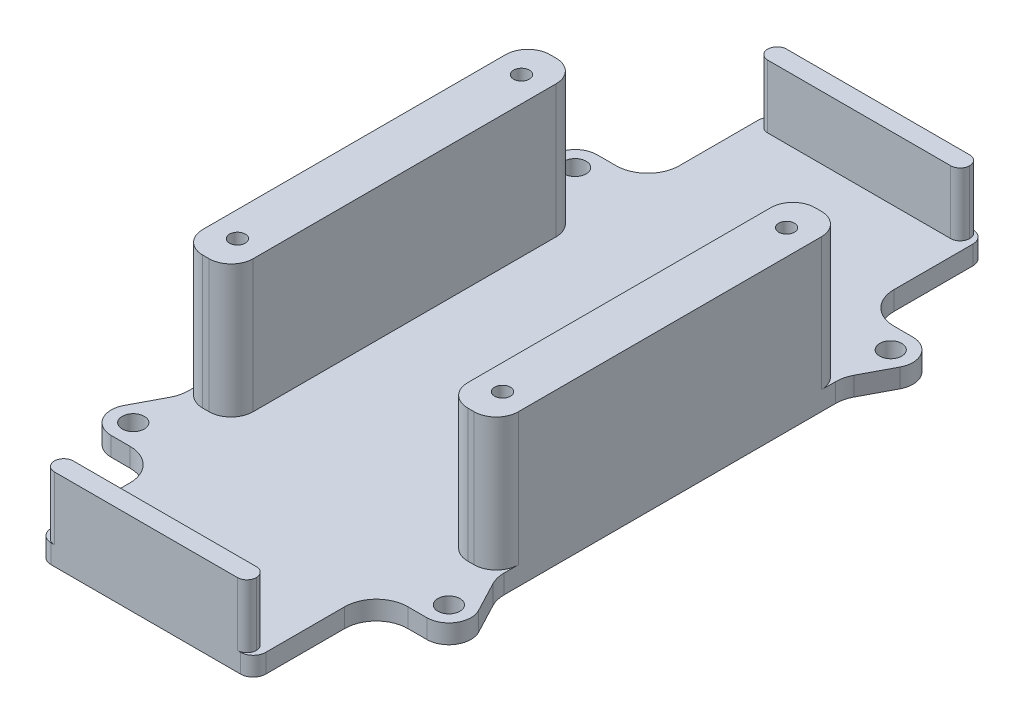
SolidWorks part; units mm, degrees
ref_plane "Спереди" through (0, 0, 0) normal (0, 0, 1) x (1, 0, 0)
ref_plane "Сверху" through (0, 0, 0) normal (0, 1, 0) x (1, 0, 0)
ref_plane "Справа" through (0, 0, 0) normal (1, 0, 0) x (0, 0, -1)
sketch "Эскиз1" plane through (0, 0, 0) normal (0, 1, 0) x (1, 0, 0)
  line L0 (0, 58) -> (0, -58) construction
  line L1 (-17, 58) -> (17, 58)
  line L2 (-25, 27.5) -> (-25, -27.5)
  line L3 (-17, -58) -> (17, -58)
  line L4 (25, 27.5) -> (25, -27.5)
  line L5 (-25, 27.5) -> (-17, 27.5)
  line L6 (-25, 0) -> (25, 0) construction
  line L7 (-17, 27.5) -> (-17, 58)
  line L8 (25, 27.5) -> (17, 27.5)
  line L9 (17, 27.5) -> (17, 58)
  line L10 (17, -27.5) -> (17, -58)
  line L11 (25, -27.5) -> (17, -27.5)
  line L12 (-17, -27.5) -> (-17, -58)
  line L13 (-25, -27.5) -> (-17, -27.5)
  point P8 (0, 0)
  dimension "D1" = 50
  dimension "D2" = 116
  dimension "D3" = 8
  dimension "D4" = 55
extrude "тело" add sketch "Эскиз1" along normal blind 3
sketch "Эскиз2" plane through (0, 3, 0) normal (0, 1, 0) x (1, 0, 0)
  line L0 (0, 58) -> (0, -58) construction
  line L3 (17, 58) -> (-17, 58) construction
  line L5 (-17, -58) -> (17, -58) construction
  line L7 (-25, 0) -> (25, 0) construction
  line L8 (-25, 27.5) -> (-25, -27.5) construction
  line L9 (25, -27.5) -> (25, 27.5) construction
  line L11 (-16, 58) -> (16, 58)
  line L12 (-16, 58) -> (-16, 55)
  line L13 (-16, 55) -> (16, 55)
  line L14 (16, 58) -> (16, 55)
  line L15 (-16, -58) -> (16, -58)
  line L16 (-16, -58) -> (-16, -55)
  line L17 (-16, -55) -> (16, -55)
  line L18 (16, -58) -> (16, -55)
  point P22 (0, 58)
  point P23 (0, -58)
  dimension "D1" = 110
  dimension "D2" = 32
extrude "выступы фиксации аккума" add sketch "Эскиз2" along normal blind 10
sketch "Эскиз9" plane through (0, 3, 0) normal (0, 1, 0) x (1, 0, 0)
  line L0 (0, 58) -> (0, -58) construction
  line L3 (-25, 0) -> (25, 0) construction
  line L5 (-25, 27.5) -> (-25, -27.5) construction
  line L6 (25, -27.5) -> (25, 27.5) construction
  line L7 (16, 58) -> (-16, 58) construction
  line L8 (-25, 27.5) -> (-17, 27.5)
  line L9 (-25, 27.5) -> (-25, -27.5)
  line L10 (-25, -27.5) -> (-17, -27.5)
  line L11 (-17, 27.5) -> (-17, -27.5)
  line L12 (25, 27.5) -> (17, 27.5)
  line L13 (25, 27.5) -> (25, -27.5)
  line L14 (25, -27.5) -> (17, -27.5)
  line L15 (17, 27.5) -> (17, -27.5)
  line L16 (-16, -58) -> (16, -58) construction
  point P20 (17, 0)
  point P21 (-17, 0)
  point P28 (0, 58)
  dimension "D1" = 34
  dimension "D2" = 55
  dimension "D3" = 8
extrude "выступы для крышки" add sketch "Эскиз9" along normal blind 21
sketch "Эскиз11" plane through (0, 24, 0) normal (0, 1, 0) x (1, 0, 0)
  line L0 (-21, 27.5) -> (-21, -27.5) construction
  line L1 (-17, 27.5) -> (-25, 27.5) construction
  line L2 (-25, -27.5) -> (-17, -27.5) construction
  line L4 (25, 27.5) -> (17, 27.5) construction
  line L5 (21, 27.5) -> (21, -27.5) construction
  line L6 (17, -27.5) -> (25, -27.5) construction
  line L8 (25, -27.5) -> (25, 27.5) construction
  line L9 (25, 0) -> (-25, 0) construction
  line L10 (-25, 27.5) -> (-25, -27.5) construction
  circle A0 centre (-21, 22.5) radius 1.25
  circle A1 centre (-21, -22.5) radius 1.25
  circle A2 centre (21, 22.5) radius 1.25
  circle A3 centre (21, -22.5) radius 1.25
  dimension "D2" = 2.5
  dimension "D1" = 45
extrude "отверстия под шурупы" cut sketch "Эскиз11" against normal blind 15
sketch "Эскиз12" plane through (0, 3, 0) normal (0, 1, 0) x (1, 0, 0)
  line L0 (0, 0) -> (0, 58) construction
  line L1 (16, 58) -> (-16, 58) construction
  line L2 (0, 0) -> (-25, 0) construction
  line L3 (-25, 27.5) -> (-25, -27.5) construction
  line L4 (-25, 27.5) -> (-28.0955, 33.3667)
  line L5 (-25, 35) -> (-17, 27.5) construction
  line L7 (-17, 58) -> (-17, 27.5) construction
  line L8 (-17, 38.5) -> (-17, 27.5)
  line L9 (-25, 27.5) -> (-17, 27.5)
  line L10 (-25, 38.5) -> (-17, 38.5)
  line L11 (25, 35) -> (17, 27.5) construction
  line L18 (25, 38.5) -> (17, 38.5)
  line L19 (25, 27.5) -> (17, 27.5)
  line L20 (17, 38.5) -> (17, 27.5)
  line L21 (25, 27.5) -> (28.0955, 33.3667)
  line L22 (25, -35) -> (17, -27.5) construction
  line L23 (-25, -35) -> (-17, -27.5) construction
  line L24 (25, -27.5) -> (28.0955, -33.3667)
  line L25 (17, -38.5) -> (17, -27.5)
  line L26 (25, -27.5) -> (17, -27.5)
  line L27 (25, -38.5) -> (17, -38.5)
  line L28 (-25, -38.5) -> (-17, -38.5)
  line L29 (-25, -27.5) -> (-17, -27.5)
  line L30 (-17, -38.5) -> (-17, -27.5)
  line L31 (-25, -27.5) -> (-28.0955, -33.3667)
  circle A0 centre (-25, 35) radius 1.75
  arc A1 (-25, 38.5) -> (-28.0955, 33.3667) centre (-25, 35) ccw
  arc A4 (25, 38.5) -> (28.0955, 33.3667) centre (25, 35) cw
  circle A5 centre (25, 35) radius 1.75
  circle A6 centre (25, -35) radius 1.75
  arc A7 (25, -38.5) -> (28.0955, -33.3667) centre (25, -35) ccw
  arc A8 (-25, -38.5) -> (-28.0955, -33.3667) centre (-25, -35) cw
  circle A9 centre (-25, -35) radius 1.75
  dimension "D1" = 7
  dimension "D2" = 3.5
  dimension "D3" = 50
  dimension "D4" = 70
extrude "Бобышка-Вытянуть6" add sketch "Эскиз12" against normal up to surface (3 mm away) up to face at (0, 0, 0)
fillet "Скругление6" radius 3.5 8 edges at (-25, 13.5, -27.5) (-17, 13.5, -27.5) (17, 13.5, -27.5) (25, 13.5, -27.5) (25, 13.5, 27.5) (17, 13.5, 27.5) (-17, 13.5, 27.5) (-25, 13.5, 27.5)
fillet "Скругление7" radius 5 8 edges at (-17, 1.5, -38.5) (-25, 1.5, -27.5) (17, 1.5, -38.5) (25, 1.5, -27.5) (25, 1.5, 27.5) (17, 1.5, 38.5) (-17, 1.5, 38.5) (-25, 1.5, 27.5)
fillet "Скругление1" radius 1.5 8 edges at (16, 8, -55) (16, 8, -58) (-16, 8, -58) (-16, 8, -55) (16, 8, 58) (16, 8, 55) (-16, 8, 55) (-16, 8, 58)
fillet "Скругление8" radius 2 4 edges at (-17, 1.5, -58) (17, 1.5, 58) (-17, 1.5, 58) (17, 1.5, -58)
